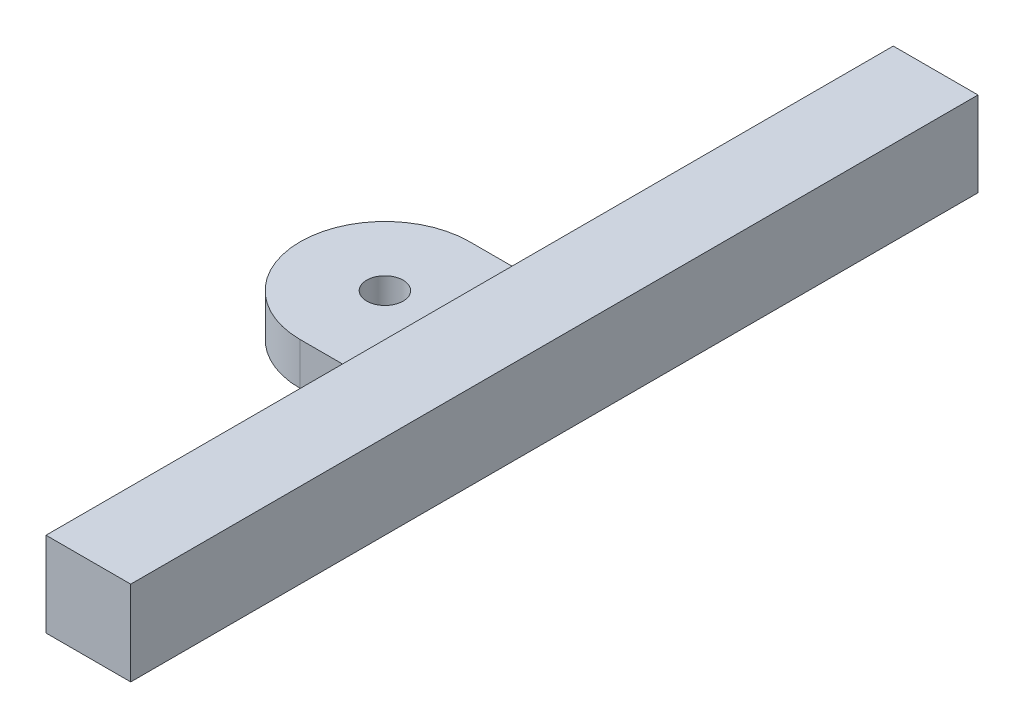
SolidWorks part; units mm, degrees
ref_plane "Plan de face" through (0, 0, 0) normal (0, 0, 1) x (1, 0, 0)
ref_plane "Plan de dessus" through (0, 0, 0) normal (0, 1, 0) x (1, 0, 0)
ref_plane "Plan de droite" through (0, 0, 0) normal (1, 0, 0) x (0, 0, -1)
sketch "Sketch1" plane through (0, 0, 0) normal (0, 1, 0) x (1, 0, 0)
  line L0 (0, 50) -> (0, -50)
  line L1 (-10, 50) -> (0, 50)
  line L2 (-10, 50) -> (-10, -50)
  line L3 (-10, -50) -> (0, -50)
  line L5 (-10, 50) -> (0, 0) construction
  line L6 (-10, -50) -> (0, 0) construction
  point P0 (0, 0)
  dimension "D1" = 10
extrude "Boss-Extrude1" add sketch "Sketch1" along normal blind 5
sketch "Sketch2" plane through (0, 5, 0) normal (0, 1, 0) x (1, 0, 0)
  line L10 (-10, 50) -> (0, 50)
  line L11 (-10, 50) -> (-10, -50)
  line L12 (-10, -50) -> (0, -50)
  line L13 (0, 50) -> (0, -50)
extrude "Boss-Extrude2" add sketch "Sketch2" along normal blind 5
sketch "Sketch3" plane through (-10, 0, 0) normal (-1, 0, 0) x (0, 0, 1)
  line L0 (0, 30) -> (0, -20) construction
  line L3 (-10, 5) -> (10, 5)
  line L4 (10, 5) -> (10, 0)
  line L5 (10, 0) -> (-10, 0)
  line L6 (-10, 0) -> (-10, 5)
  point P9 (0, 5)
  dimension "D1" = 20
  dimension "D2" = 30
extrude "Boss-Extrude3" add sketch "Sketch3" along normal blind 20
fillet "Fillet1" radius 10 2 edges at (-30, 2.5, 10) (-30, 2.5, -10)
sketch "Sketch4" plane through (0, 5, 0) normal (0, 1, 0) x (1, 0, 0)
  circle A0 centre (-20, 0) radius 2.15
  dimension "D1" = 4.3
extrude "Cut-Extrude1" cut sketch "Sketch4" against normal up to next
